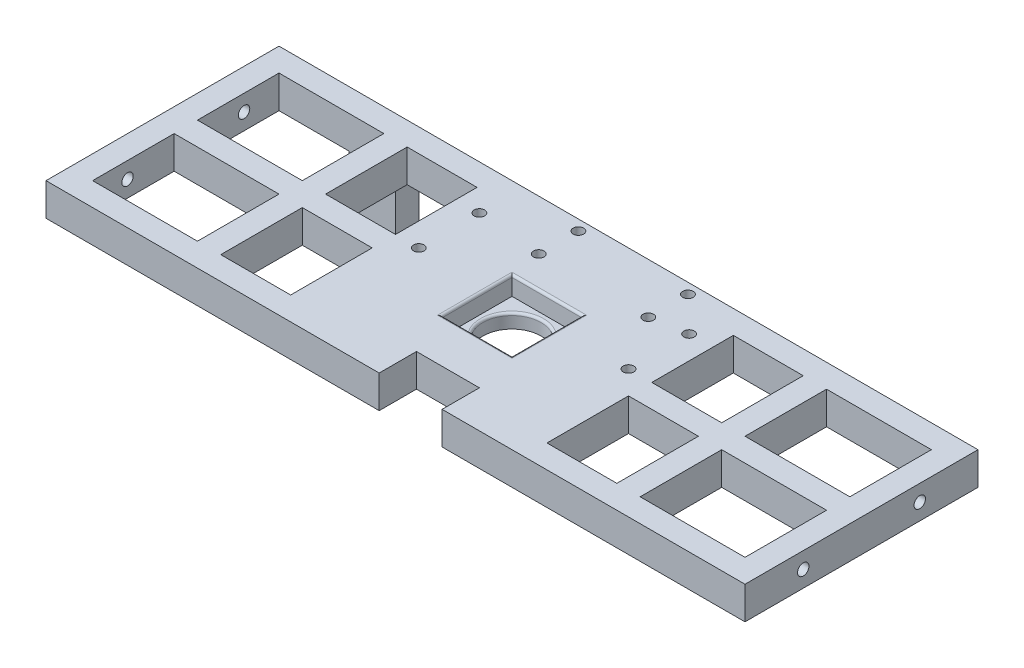
SolidWorks part; units mm, degrees
ref_plane "前视基准面" through (0, 0, 0) normal (0, 0, 1) x (1, 0, 0)
ref_plane "上视基准面" through (0, 0, 0) normal (0, 1, 0) x (1, 0, 0)
ref_plane "右视基准面" through (0, 0, 0) normal (1, 0, 0) x (0, 0, -1)
sketch "草图1" plane through (0, 0, 0) normal (0, 1, 0) x (1, 0, 0)
  line L1 (0, 0) -> (-300, 0)
  line L2 (0, 0) -> (0, 100)
  line L3 (0, 100) -> (-300, 100)
  line L4 (-300, 0) -> (-300, 100)
  dimension "D1" = 300
  dimension "D2" = 100
extrude "凸台-拉伸1" add sketch "草图1" along normal blind 16
sketch "草图2" plane through (0, 16, 0) normal (0, 1, 0) x (1, 0, 0)
  line L0 (-150, 100) -> (-150, 50) construction
  line L1 (0, 100) -> (-300, 100) construction
  line L2 (-300, 50) -> (-150, 50) construction
  line L3 (-300, 100) -> (-300, 0) construction
  line L5 (-165, 65) -> (-135, 65)
  line L6 (-165, 65) -> (-165, 35)
  line L7 (-165, 35) -> (-135, 35)
  line L8 (-135, 65) -> (-135, 35)
  line L9 (-165, 65) -> (-135, 35) construction
  line L10 (-165, 35) -> (-135, 65) construction
  dimension "D1" = 50
  dimension "D2" = 30
  dimension "D3" = 30
extrude "切除-拉伸1" cut sketch "草图2" against normal blind 8
sketch "草图3" plane through (0, 8, 0) normal (0, 1, 0) x (1, 0, 0)
  line L0 (-135, 65) -> (-165, 65) construction
  line L1 (-135, 35) -> (-135, 65) construction
  circle A0 centre (-150, 50) radius 12.5
  dimension "D3" = 25
  dimension "D1" = 15
  dimension "D2" = 15
extrude "切除-拉伸2" cut sketch "草图3" against normal blind 14
sketch "草图4" plane through (0, 16, 0) normal (0, 1, 0) x (1, 0, 0)
  line L0 (-165, 65) -> (-165, 35) construction
  line L1 (-295, 90) -> (-245, 90)
  line L2 (-295, 90) -> (-295, 55)
  line L3 (-295, 55) -> (-245, 55)
  line L4 (-245, 90) -> (-245, 55)
  line L5 (-295, 45) -> (-245, 45)
  line L6 (-295, 45) -> (-295, 10)
  line L7 (-295, 10) -> (-245, 10)
  line L8 (-245, 45) -> (-245, 10)
  line L9 (-235, 90) -> (-185, 90)
  line L10 (-235, 90) -> (-235, 55)
  line L11 (-235, 55) -> (-185, 55)
  line L12 (-185, 90) -> (-185, 55)
  line L13 (-235, 45) -> (-185, 45)
  line L14 (-235, 45) -> (-235, 10)
  line L15 (-235, 10) -> (-185, 10)
  line L16 (-185, 45) -> (-185, 10)
  line L17 (0, 100) -> (-300, 100) construction
  line L18 (-300, 0) -> (0, 0) construction
  line L19 (-300, 100) -> (-300, 0) construction
  line L20 (-150, 100) -> (-150, 73.2626) construction
  line L21 (-5, 10) -> (-55, 10)
  line L22 (-55, 45) -> (-55, 10)
  line L23 (-5, 45) -> (-55, 45)
  line L24 (-5, 45) -> (-5, 10)
  line L25 (-65, 10) -> (-115, 10)
  line L26 (-115, 45) -> (-115, 10)
  line L27 (-65, 45) -> (-115, 45)
  line L28 (-65, 45) -> (-65, 10)
  line L29 (-65, 55) -> (-115, 55)
  line L30 (-115, 90) -> (-115, 55)
  line L31 (-65, 90) -> (-115, 90)
  line L32 (-65, 90) -> (-65, 55)
  line L33 (-5, 55) -> (-55, 55)
  line L34 (-55, 90) -> (-55, 55)
  line L35 (-5, 90) -> (-55, 90)
  line L36 (-5, 90) -> (-5, 55)
  dimension "D1" = 20
  dimension "D2" = 20
  dimension "D3" = 10
  dimension "D4" = 10
  dimension "D5" = 10
  dimension "D6" = 35
  dimension "D7" = 10
  dimension "D8" = 10
  dimension "D9" = 5
  dimension "D10" = 5
  dimension "D11" = 35
  dimension "D12" = 35
  dimension "D13" = 50
  dimension "D14" = 50
  dimension "D15" = 50
  dimension "D16" = 50
extrude "切除-拉伸3" cut sketch "草图4" against normal up to next
sketch "草图7" plane through (-185, 0, 0) normal (-1, 0, 0) x (0, 0, 1)
  line L0 (-45, 0) -> (-10, 0) construction
  line L1 (-10, 0) -> (-10, 16) construction
  line L2 (-10, 16) -> (-45, 16) construction
  line L3 (-45, 16) -> (-45, 0) construction
  line L4 (-90, 0) -> (-55, 0) construction
  line L5 (-55, 0) -> (-55, 16) construction
  line L6 (-55, 16) -> (-90, 16) construction
  line L7 (-90, 16) -> (-90, 0) construction
  line L8 (-45, 0) -> (-10, 0)
  line L9 (-10, 0) -> (-10, 16)
  line L10 (-10, 16) -> (-45, 16)
  line L11 (-45, 16) -> (-45, 0)
  line L12 (-90, 0) -> (-55, 0)
  line L13 (-55, 0) -> (-55, 16)
  line L14 (-55, 16) -> (-90, 16)
  line L15 (-90, 16) -> (-90, 0)
extrude "凸台-拉伸2" add sketch "草图7" along normal blind 20
sketch "草图8" plane through (-115, 0, 0) normal (1, 0, 0) x (0, 0, -1)
  line L0 (10, 0) -> (45, 0) construction
  line L1 (45, 0) -> (45, 16) construction
  line L2 (45, 16) -> (10, 16) construction
  line L3 (10, 16) -> (10, 0) construction
  line L4 (55, 0) -> (90, 0) construction
  line L5 (90, 0) -> (90, 16) construction
  line L6 (90, 16) -> (55, 16) construction
  line L7 (55, 16) -> (55, 0) construction
  line L8 (10, 0) -> (45, 0)
  line L9 (45, 0) -> (45, 16)
  line L10 (45, 16) -> (10, 16)
  line L11 (10, 16) -> (10, 0)
  line L12 (55, 0) -> (90, 0)
  line L13 (90, 0) -> (90, 16)
  line L14 (90, 16) -> (55, 16)
  line L15 (55, 16) -> (55, 0)
extrude "凸台-拉伸3" add sketch "草图8" along normal blind 20
sketch "草图9" plane through (0, 0, 0) normal (0, -1, 0) x (1, 0, 0)
  line L5 (-295, -90) -> (-245, -90) construction
  line L10 (-260, -90) -> (-240, -90)
  line L20 (-260, -90) -> (-260, -100)
  line L21 (-260, -100) -> (-240, -100)
  line L22 (-240, -90) -> (-240, -100)
  line L23 (0, -100) -> (-300, -100) construction
  line L24 (-300, -100) -> (-300, 0) construction
  dimension "D3" = 20
  dimension "D4" = 40
extrude "凸台-拉伸4" add sketch "草图9" along normal blind 25
fillet "圆角1" radius 1 1 edges at (-150, 8, -37.5)
fillet "圆角2" radius 1 4 edges at (-135, 16, -50) (-150, 16, -65) (-150, 16, -35) (-165, 16, -50)
sketch "草图13" plane through (-5, 0, 0) normal (-1, 0, 0) x (0, 0, 1)
  line L0 (-90, 0) -> (-55, 0) construction
  line L1 (-55, 0) -> (-55, 16) construction
  line L2 (-55, 16) -> (-90, 16) construction
  line L3 (-90, 16) -> (-90, 0) construction
  line L4 (-45, 0) -> (-10, 0) construction
  line L5 (-10, 0) -> (-10, 16) construction
  line L6 (-10, 16) -> (-45, 16) construction
  line L7 (-45, 16) -> (-45, 0) construction
  line L8 (-90, 0) -> (-55, 0)
  line L9 (-55, 0) -> (-55, 16)
  line L10 (-55, 16) -> (-90, 16)
  line L11 (-90, 16) -> (-90, 0)
  line L12 (-45, 0) -> (-10, 0)
  line L13 (-10, 0) -> (-10, 16)
  line L14 (-10, 16) -> (-45, 16)
  line L15 (-45, 16) -> (-45, 0)
extrude "凸台-拉伸6" add sketch "草图13" along normal blind 4
sketch "草图14" plane through (-295, 0, 0) normal (1, 0, 0) x (0, 0, -1)
  line L0 (55, 0) -> (90, 0) construction
  line L1 (90, 0) -> (90, 16) construction
  line L2 (90, 16) -> (55, 16) construction
  line L3 (55, 16) -> (55, 0) construction
  line L4 (10, 0) -> (45, 0) construction
  line L5 (45, 0) -> (45, 16) construction
  line L6 (45, 16) -> (10, 16) construction
  line L7 (10, 16) -> (10, 0) construction
  line L8 (55, 0) -> (90, 0)
  line L9 (90, 0) -> (90, 16)
  line L10 (90, 16) -> (55, 16)
  line L11 (55, 16) -> (55, 0)
  line L12 (10, 0) -> (45, 0)
  line L13 (45, 0) -> (45, 16)
  line L14 (45, 16) -> (10, 16)
  line L15 (10, 16) -> (10, 0)
extrude "凸台-拉伸7" add sketch "草图14" along normal blind 4
sketch "草图17" plane through (-291, 0, 0) normal (1, 0, 0) x (0, 0, -1)
  line L0 (10, 16) -> (10, 0) construction
  line L1 (10, 0) -> (45, 0) construction
  line L2 (45, 0) -> (45, 16) construction
  line L3 (45, 16) -> (10, 16) construction
  line L4 (55, 16) -> (55, 0) construction
  line L5 (55, 0) -> (90, 0) construction
  line L6 (90, 0) -> (90, 16) construction
  line L7 (90, 16) -> (55, 16) construction
  line L8 (10, 16) -> (10, 0)
  line L9 (10, 0) -> (45, 0)
  line L10 (45, 0) -> (45, 16)
  line L11 (45, 16) -> (10, 16)
  line L12 (55, 16) -> (55, 0)
  line L13 (55, 0) -> (90, 0)
  line L14 (90, 0) -> (90, 16)
  line L15 (90, 16) -> (55, 16)
extrude "凸台-拉伸8" add sketch "草图17" along normal blind 1
sketch "草图18" plane through (-9, 0, 0) normal (-1, 0, 0) x (0, 0, 1)
  line L0 (-45, 16) -> (-45, 0) construction
  line L1 (-45, 0) -> (-10, 0) construction
  line L2 (-10, 0) -> (-10, 16) construction
  line L3 (-10, 16) -> (-45, 16) construction
  line L4 (-90, 16) -> (-90, 0) construction
  line L5 (-90, 0) -> (-55, 0) construction
  line L6 (-55, 0) -> (-55, 16) construction
  line L7 (-55, 16) -> (-90, 16) construction
  line L8 (-45, 16) -> (-45, 0)
  line L9 (-45, 0) -> (-10, 0)
  line L10 (-10, 0) -> (-10, 16)
  line L11 (-10, 16) -> (-45, 16)
  line L12 (-90, 16) -> (-90, 0)
  line L13 (-90, 0) -> (-55, 0)
  line L14 (-55, 0) -> (-55, 16)
  line L15 (-55, 16) -> (-90, 16)
extrude "凸台-拉伸9" add sketch "草图18" along normal blind 1
sketch "草图24" [suppressed] plane through (0, 16, 0) normal (0, 1, 0) x (1, 0, 0)
  circle A0 centre (-195, 81) radius 2.25
  circle A1 centre (-205, 54.9815) radius 2.25
  circle A2 centre (-105, 81) radius 2.25
  circle A3 centre (-115, 54.9815) radius 2.25
  dimension "D1" = 4.5
  dimension "D2" = 4.5
  dimension "D3" = 4.5
  dimension "D4" = 4.5
extrude "切除-拉伸13" [suppressed] cut sketch "草图24" against normal blind 5
sketch "草图26" plane through (0, 0, 0) normal (0, -1, 0) x (1, 0, 0)
  line L12 (-260, -90) -> (-290, -90)
  line L13 (-290, -90) -> (-290, -55)
  line L14 (-290, -55) -> (-245, -55)
  line L15 (-245, -55) -> (-245, -90)
  line L16 (-245, -90) -> (-240, -90)
  line L17 (-240, -90) -> (-240, -100)
  line L18 (-240, -100) -> (0, -100)
  line L19 (0, -100) -> (0, 0)
  line L20 (0, 0) -> (-300, 0)
  line L21 (-300, 0) -> (-300, -100)
  line L22 (-300, -100) -> (-260, -100)
  line L23 (-260, -100) -> (-260, -90)
  line L24 (-260, -90) -> (-290, -90)
  line L25 (-290, -90) -> (-290, -55)
  line L26 (-290, -55) -> (-245, -55)
  line L27 (-245, -55) -> (-245, -90)
  line L28 (-245, -90) -> (-240, -90)
  line L29 (-240, -90) -> (-240, -100)
  line L30 (-240, -100) -> (0, -100)
  line L31 (0, -100) -> (0, 0)
  line L32 (0, 0) -> (-300, 0)
  line L33 (-300, 0) -> (-300, -100)
  line L34 (-300, -100) -> (-260, -100)
  line L35 (-260, -100) -> (-260, -90)
  dimension "D1" = 0
extrude "切除-拉伸15" cut sketch "草图26" against normal blind 2
sketch "草图28" plane through (0, 16, 0) normal (0, 1, 0) x (1, 0, 0)
  line L0 (-205, 55) -> (-205, 90) construction
  line L1 (0, 100) -> (-300, 100) construction
  line L2 (-95, 90) -> (-95, 55) construction
  circle A8 centre (-105.0028, 55) radius 2.25
  circle A9 centre (-105, 81) radius 2.25
  circle A10 centre (-120, 78.5) radius 2.25
  circle A11 centre (-120, 95.5) radius 2.25
  circle A12 centre (-167.0001, 78.5) radius 2.25
  circle A13 centre (-167.0001, 95.5) radius 2.25
  circle A14 centre (-195, 55) radius 2.25
  circle A15 centre (-195, 81) radius 2.25
  dimension "D1" = 10
  dimension "D2" = 10
  dimension "D3" = 26
  dimension "D4" = 19
  dimension "D5" = 4.5
  dimension "D6" = 4.5
  dimension "D7" = 17
  dimension "D8" = 4.5
  dimension "D9" = 4.5
  dimension "D10" = 17
  dimension "D11" = 47.0001
  dimension "D12" = 47.0001
  dimension "D13" = 4.5
  dimension "D14" = 4.5
  dimension "D15" = 4.5
  dimension "D16" = 4.5
  dimension "D17" = 25
  dimension "D18" = 25
  dimension "D19" = 10
  dimension "D20" = 10.0028
  dimension "D21" = 26
  dimension "D22" = 19
  dimension "D23" = 4.5
  dimension "D24" = 4.5
extrude "切除-拉伸18" cut sketch "草图28" against normal blind 5
sketch "草图30" plane through (0, 11, 0) normal (0, 1, 0) x (1, 0, 0)
  circle A2 centre (-195, 81) radius 1.5
  circle A3 centre (-195, 55) radius 1.5
  circle A4 centre (-167.0001, 95.5) radius 1.5
  circle A5 centre (-167.0001, 78.5) radius 1.5
  circle A6 centre (-120, 95.5) radius 1.5
  circle A7 centre (-120, 78.5) radius 1.5
  circle A8 centre (-105, 81) radius 1.5
  circle A9 centre (-105.0028, 55) radius 1.5
  dimension "D1" = 3
extrude "切除-拉伸20" cut sketch "草图30" against normal blind 4
sketch "草图33" plane through (-300, 0, 0) normal (-1, 0, 0) x (0, 0, 1)
  line L0 (-100, 16) -> (0, 16) construction
  line L3 (-100, 16) -> (-100, 2) construction
  line L4 (0, 16) -> (0, 2) construction
  circle A0 centre (-75, 9) radius 2.45
  circle A1 centre (-25, 9) radius 2.45
  dimension "D1" = 7
  dimension "D2" = 7
  dimension "D3" = 4.9
  dimension "D4" = 4.9
  dimension "D5" = 25
  dimension "D6" = 25
extrude "切除-拉伸22" cut sketch "草图33" against normal blind 13.2
sketch "草图34" plane through (0, 0, 0) normal (1, 0, 0) x (0, 0, -1)
  circle A0 centre (75, 9) radius 2.45 construction
  circle A1 centre (25, 9) radius 2.45 construction
  circle A2 centre (75, 9) radius 2.45
  circle A3 centre (25, 9) radius 2.45
extrude "切除-拉伸23" cut sketch "草图34" against normal blind 13.2
sketch "草图35" plane through (0, 16, 0) normal (0, 1, 0) x (1, 0, 0)
  line L1 (0, 0) -> (0, 100) construction
  line L2 (-300, 0) -> (0, 0) construction
  line L3 (-157, 0) -> (-130, 0)
  line L4 (-157, 0) -> (-157, 16)
  line L5 (-157, 16) -> (-130, 16)
  line L6 (-130, 0) -> (-130, 16)
  dimension "D1" = 130
  dimension "D2" = 27
  dimension "D3" = 16
extrude "切除-拉伸24" cut sketch "草图35" against normal blind 20
